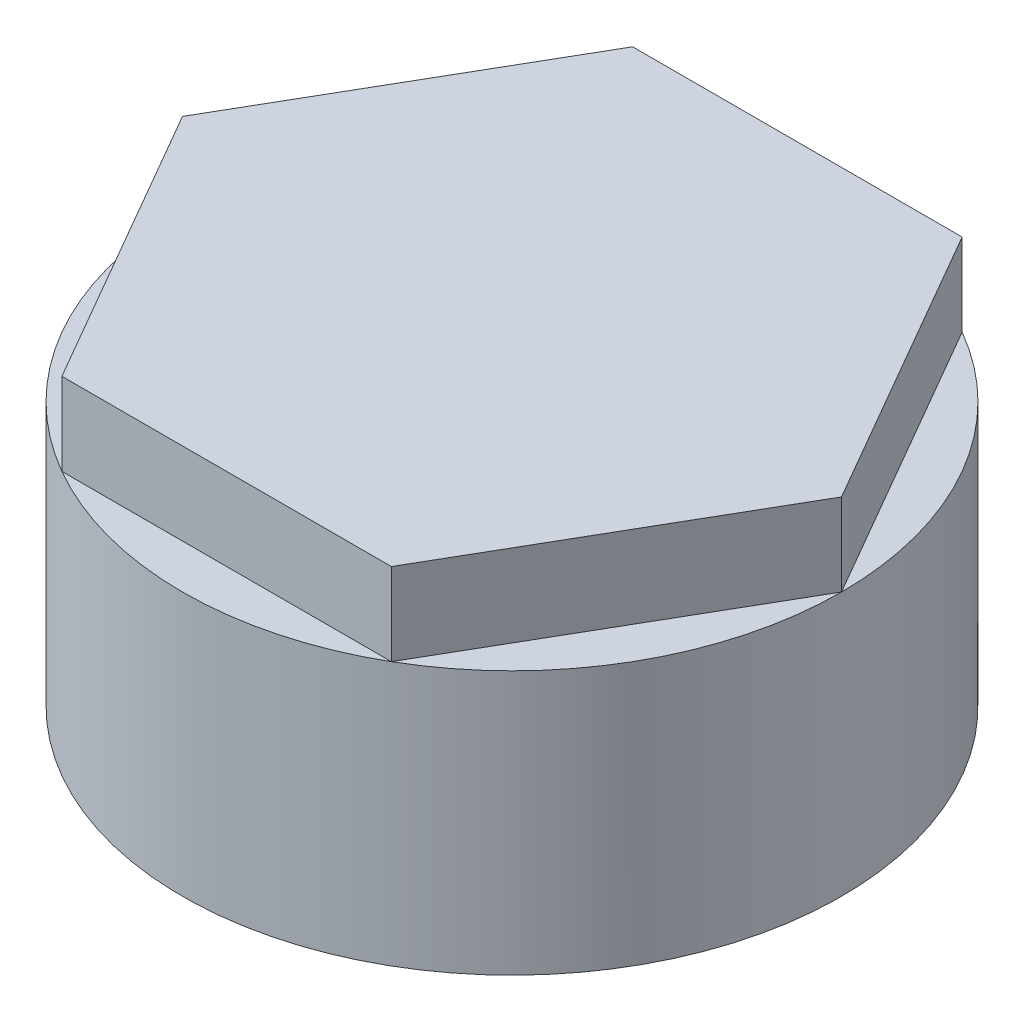
SolidWorks part; units mm, degrees
material "1.0035 (S185)"
ref_plane "Piano frontale" through (0, 0, 0) normal (0, 0, 1) x (1, 0, 0)
ref_plane "Piano superiore" through (0, 0, 0) normal (0, 1, 0) x (1, 0, 0)
ref_plane "Piano destro" through (0, 0, 0) normal (1, 0, 0) x (0, 0, -1)
sketch "Schizzo1" plane through (0, 0, 0) normal (0, 0, 1) x (1, 0, 0)
  line L0 (-15.5465, 0) -> (-15.5465, 15)
  line L1 (-15.5465, 15) -> (0, 15)
  line L2 (0, 15) -> (0, 21)
  line L3 (0, 21) -> (-20, 21)
  line L4 (-20, 21) -> (-20, 0)
  line L5 (-20, 0) -> (-15.5465, 0)
  line L6 (0, 0) -> (0, 29.0615) construction
  dimension "D1" = 40
  dimension "D2" = 31.093
  dimension "D3" = 21
  dimension "D4" = 15
revolve "Rivoluzione1" add sketch "Schizzo1" angle 360 about L6
cosmetic thread "Filettatura cosmetica1" parameters "D1"=14.9999, "D2"=36
sketch "Schizzo2" plane through (0, 21, 0) normal (0, 1, 0) x (1, 0, 0)
  line L0 (-10, 17.3205) -> (10, 17.3205)
  line L1 (10, 17.3205) -> (20, 0)
  line L2 (20, 0) -> (10, -17.3205)
  line L3 (10, -17.3205) -> (-10, -17.3205)
  line L4 (-10, -17.3205) -> (-20, 0)
  line L5 (-20, 0) -> (-10, 17.3205)
  circle A0 centre (0, 0) radius 20
  circle A1 centre (0, 0) radius 20 construction
  circle M8 centre (0, 0) radius 20
extrude "Taglio-Estrusione1" cut sketch "Schizzo2" against normal blind 5 contours L5 M8 | L4 M8 | L3 M8 | L2 M8 | L1 M8 | L0 M8 region at (0, 21, -18.3987) region at (-15.9337, 21, -9.1994) region at (15.9337, 21, -9.1994) region at (-15.9337, 21, 9.1994) region at (15.9337, 21, 9.1994) region at (0, 21, 18.3987)
equation "\"17.5.00mm\"=5000"
